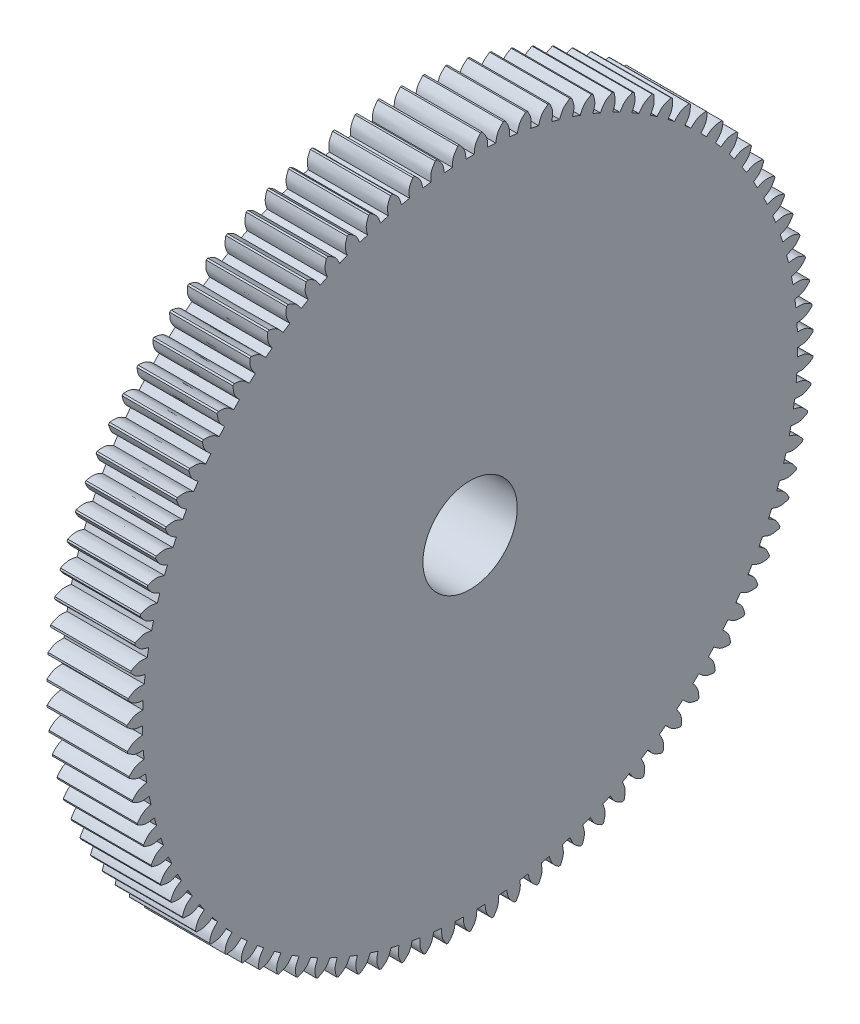
SolidWorks part; units mm, degrees
ref_plane "Front" through (0, 0, 0) normal (0, 0, 1) x (1, 0, 0)
ref_plane "Top" through (0, 0, 0) normal (0, 1, 0) x (1, 0, 0)
ref_plane "Right" through (0, 0, 0) normal (1, 0, 0) x (0, 0, -1)
sketch "Ritning 1" plane through (0, 0, 0) normal (0, 0, 1) x (1, 0, 0)
  line L0 (-8.5, -36.375) -> (8.5, -36.375) construction
  line L1 (-8.5, -26.375) -> (8.5, -26.375)
  line L2 (8.5, 36.375) -> (8.5, -26.375)
  line L3 (8.5, 36.375) -> (-8.5, 36.375)
  line L4 (-8.5, 36.375) -> (-8.5, -26.375)
  line L5 (-8.5, -26.375) -> (-8.5, -36.375) construction
  line L6 (-8.5, -36.375) -> (8.5, -36.375) construction
  dimension "D1" = 8.5
  dimension "D2" = 8.5
  dimension "D3" = 36.375
  dimension "D4" = 26.375
  dimension "D5" = 36.375
revolve "Kugghjulsämne" add sketch "Ritning 1" angle 360 about L0
sketch "Ritning 2" plane through (-8.5, 0, 0) normal (-1, 0, 0) x (0, 0, 1)
  line L0 (0, -36.375) -> (0, 36.375) construction
  line L1 (2.2117, 36.3414) -> (0, 38.5531)
  line L2 (-2.2117, 36.3414) -> (0, 38.5531)
  line L3 (0, -36.375) -> (9.7324, -36.375) construction
  arc A0 (0.8615, 33.0697) -> (-0.8615, 33.0697) centre (0, -36.375) ccw
  circle A1 centre (0, -36.375) radius 72.75 construction
  spline S0 degree 3 poles (2.2117, 36.3414) (1.8075, 35.8741) (0.9942, 34.9339) (0.9059, 33.6935) (0.8615, 33.0697) knots 0 0 0 0 0.497062 1 1 1 1
  spline S1 degree 3 poles (-2.2117, 36.3414) (-1.8075, 35.8741) (-0.9942, 34.9339) (-0.9059, 33.6935) (-0.8615, 33.0697) knots 0 0 0 0 0.497062 1 1 1 1
  dimension "D1" = 69.45
  dimension "D2" = 0.8615
  dimension "D3" = 1.1781
  dimension "D4" = 2.2117
  dimension "D5" = 71.2403
  dimension "D6" = 1.1781
  dimension "D7" = 72.7164
extrude "Kugglucka" cut sketch "Ritning 2" against normal up to surface (17 mm away) up to face at (8.5, -36.375, 72.75)
pattern_circular "CirPattern" count 95 over 360 about axis through (-8.5, -36.375, 0) along (-1, 0, 0) of "Kugglucka"
